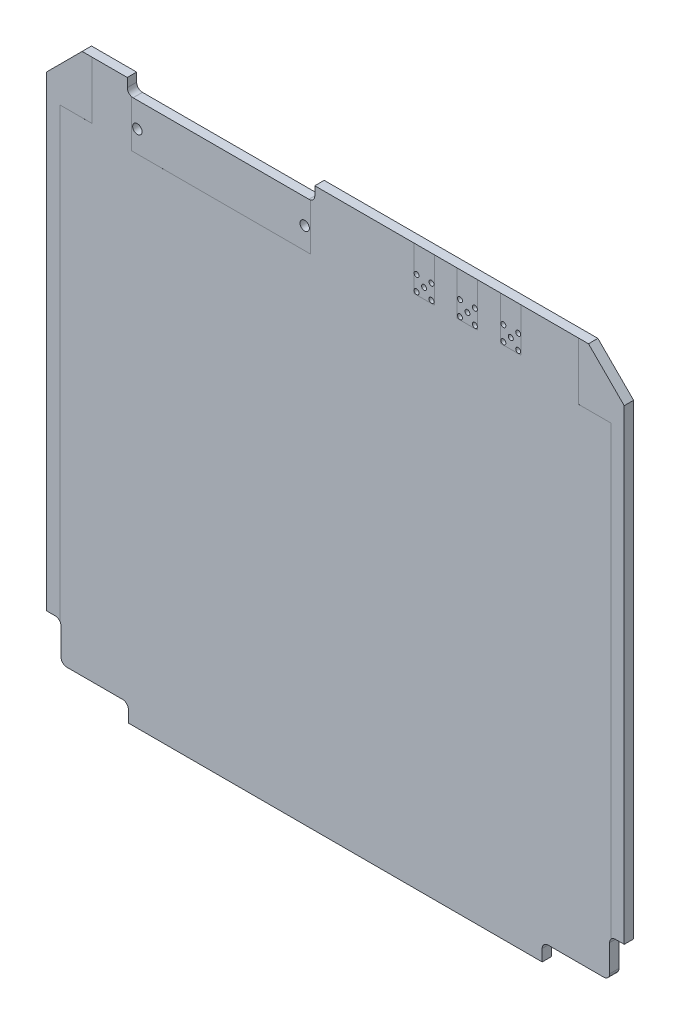
SolidWorks part; units mm, degrees
ref_plane "Front Plane" through (0, 0, 0) normal (0, 0, 1) x (1, 0, 0)
ref_plane "Top Plane" through (0, 0, 0) normal (0, 1, 0) x (1, 0, 0)
ref_plane "Right Plane" through (0, 0, 0) normal (1, 0, 0) x (0, 0, -1)
ref_plane "Plane4" through (0, 0, -0.0125) normal (0, 0, -1) x (-1, 0, 0)
sketch "Sketch1" plane through (0, 0, -0.0125) normal (0, 0, -1) x (-1, 0, 0)
  line L0 (35.3, -50) -> (35.3, -48)
  line L1 (36.3, -47) -> (45.8, -47)
  line L2 (46.8, -46) -> (46.8, -41.4)
  line L3 (47.8, -40.4) -> (49.3, -40.4)
  line L4 (49.3, -40.4) -> (49.3, 39.2)
  line L5 (49.3, 39.2) -> (43.2, 45.3)
  line L6 (43.2, 45.3) -> (35.5, 45.3)
  line L7 (35.5, 45.3) -> (35.5, 43.8)
  line L8 (34.5, 42.8) -> (4.5, 42.8)
  line L9 (3.5, 43.8) -> (3.5, 45.3)
  line L10 (3.5, 45.3) -> (-43.2, 45.3)
  line L11 (-43.2, 45.3) -> (-49.3, 39.2)
  line L12 (-49.3, 39.2) -> (-49.3, -40.4)
  line L13 (-49.3, -40.4) -> (-47.8, -40.4)
  line L14 (-46.8, -41.4) -> (-46.8, -46)
  line L15 (-45.8, -47) -> (-36.3, -47)
  line L16 (-35.3, -48) -> (-35.3, -50)
  line L17 (-35.3, -50) -> (35.3, -50)
  line L18 (0, -50) -> (0, 45.3) construction
  line L19 (19.5, 42.8) -> (19.5, 25.5258) construction
  line L20 (-13.87, 40.87) -> (-16.41, 38.33) construction
  line L21 (-21.27, 40.87) -> (-23.81, 38.33) construction
  line L22 (-28.67, 40.87) -> (-31.21, 38.33) construction
  arc A0 (35.3, -48) -> (36.3, -47) centre (36.3, -48) cw
  arc A1 (45.8, -47) -> (46.8, -46) centre (45.8, -46) ccw
  arc A2 (46.8, -41.4) -> (47.8, -40.4) centre (47.8, -41.4) cw
  arc A3 (35.5, 43.8) -> (34.5, 42.8) centre (34.5, 43.8) cw
  arc A4 (4.5, 42.8) -> (3.5, 43.8) centre (4.5, 43.8) cw
  arc A5 (-47.8, -40.4) -> (-46.8, -41.4) centre (-47.8, -41.4) cw
  arc A6 (-46.8, -46) -> (-45.8, -47) centre (-45.8, -46) ccw
  arc A7 (-36.3, -47) -> (-35.3, -48) centre (-36.3, -48) cw
  circle A8 centre (-21.27, 40.87) radius 0.425
  circle A9 centre (-23.81, 40.87) radius 0.425
  circle A10 centre (-22.54, 39.6) radius 0.425
  circle A11 centre (-13.87, 40.87) radius 0.425
  circle A12 centre (-23.81, 38.33) radius 0.425
  circle A13 centre (-16.41, 40.87) radius 0.425
  circle A14 centre (-15.14, 39.6) radius 0.425
  circle A15 centre (-21.27, 38.33) radius 0.425
  circle A16 centre (-28.67, 40.87) radius 0.425
  circle A17 centre (-31.21, 40.87) radius 0.425
  circle A18 centre (-16.41, 38.33) radius 0.425
  circle A19 centre (-29.94, 39.6) radius 0.425
  circle A20 centre (-31.21, 38.33) radius 0.425
  circle A21 centre (-28.67, 38.33) radius 0.425
  circle A22 centre (33.775, 38.54) radius 0.8
  circle A23 centre (5.225, 38.54) radius 0.8
  circle A24 centre (-13.87, 38.33) radius 0.425
  point P35 (-15.14, 39.6)
  dimension "D7" = 2.5
  dimension "D8" = 1.6
  dimension "D9" = 14.275
  dimension "D10" = 4.26
  dimension "D11" = 1
  dimension "D12" = 1
  dimension "D13" = 1
  dimension "D14" = 1
  dimension "D15" = 1
  dimension "D16" = 1
  dimension "D17" = 1
  dimension "D18" = 1
  dimension "D26" = 0.85
  dimension "D1" = 98.6
  dimension "D2" = 95.3
  dimension "D3" = 14
  dimension "D4" = 9.6
  dimension "D5" = 2.5
  dimension "D6" = 3
  dimension "D19" = 14
  dimension "D20" = 2.5
  dimension "D21" = 6.1
  dimension "D22" = 6.1
  dimension "D23" = 32
  dimension "D24" = 2.54
  dimension "D25" = 2.54
  dimension "D28" = 7.4
  dimension "D29" = 4.43
  dimension "D30" = 35.43
  dimension "D31" = 45
  dimension "D32" = 45
  dimension "D33" = 29.8
  dimension "D34" = 50
  dimension "D27" = 3
extrude "Boss-Extrude1" add sketch "Sketch1" against normal blind 1.6
sketch "thermalContacts_lower" plane through (0, 0, -0.0125) normal (0, 0, -1) x (-1, 0, 0)
  line L0 (-47, 35.5) -> (-47, -41.5) construction
  line L1 (-41.5, 35.5) -> (-41.5, 41.5) construction
  line L2 (-41.5, 35.5) -> (-47, 35.5) construction
  line L3 (-47, 35.5) -> (-47, -41.5)
  line L4 (-41.5, 35.5) -> (-41.5, 41.5)
  line L5 (-41.5, 35.5) -> (-47, 35.5)
  line L6 (47, 35.5) -> (47, -41.5) construction
  line L7 (41.5, 35.5) -> (47, 35.5) construction
  line L8 (41.5, 35.5) -> (41.5, 41.5) construction
  line L9 (47, 35.5) -> (47, -41.5)
  line L10 (41.5, 35.5) -> (47, 35.5)
  line L11 (41.5, 35.5) -> (41.5, 41.5)
  line L12 (41.5, 41.5) -> (41.5, 47) construction
  line L13 (41.5, 41.5) -> (49.5, 41.5) construction
  line L14 (41.5, 41.5) -> (41.5, 47)
  line L15 (41.5, 41.5) -> (49.5, 41.5) construction
  line L16 (-41.5, 41.5) -> (-41.5, 47) construction
  line L17 (-41.5, 41.5) -> (-49.5, 41.5) construction
  line L18 (-41.5, 41.5) -> (-41.5, 47)
  line L19 (-41.5, 41.5) -> (-49.5, 41.5) construction
  line L20 (47, -41.5) -> (59.8273, -41.5)
  line L21 (59.8273, -41.5) -> (59.8273, 47)
  line L22 (59.8273, 47) -> (41.5, 47)
  line L23 (-41.5, 47) -> (-56.1922, 47)
  line L24 (-56.1922, 47) -> (-56.1922, -41.5)
  line L25 (-56.1922, -41.5) -> (-47, -41.5)
sketch "thermalContacts_upper" plane through (0, 0, 1.5875) normal (0, 0, 1) x (1, 0, 0)
  line L3 (-47, 35.5) -> (-47, -41.5)
  line L4 (-41.5, 35.5) -> (-41.5, 41.5)
  line L5 (-41.5, 35.5) -> (-47, 35.5)
  line L9 (47, 35.5) -> (47, -41.5)
  line L10 (41.5, 35.5) -> (47, 35.5)
  line L11 (41.5, 35.5) -> (41.5, 41.5)
  line L14 (41.5, 41.5) -> (41.5, 47)
  line L15 (41.5, 41.5) -> (49.5, 41.5) construction
  line L18 (-41.5, 41.5) -> (-41.5, 47)
  line L19 (-41.5, 41.5) -> (-49.5, 41.5) construction
  line L20 (47, -41.5) -> (59.8273, -41.5)
  line L21 (59.8273, -41.5) -> (59.8273, 47)
  line L22 (59.8273, 47) -> (41.5, 47)
  line L23 (-41.5, 47) -> (-56.1922, 47)
  line L24 (-56.1922, 47) -> (-56.1922, -41.5)
  line L25 (-56.1922, -41.5) -> (-47, -41.5)
extrude "Cut-Extrude1" cut sketch "thermalContacts_lower" against normal blind 0.0001
extrude "Cut-Extrude2" cut sketch "thermalContacts_upper" against normal blind 0.0001
sketch "partFootprints" plane through (0, 0, 1.5875) normal (0, 0, 1) x (1, 0, 0)
  line L0 (-34.74, 34.84) -> (-34.74, 42.8292)
  line L1 (-4.26, 34.84) -> (-34.74, 34.84)
  line L2 (-41.5, 45.3) -> (-35.5, 45.3) construction
  line L3 (-36.1132, 45.3) -> (-39.5054, 45.3) construction
  line L4 (-4.26, 34.84) -> (-4.26, 42.8292)
  line L5 (-49.3, -40.4) -> (-49.3, 39.2) construction
  line L6 (13.39, 45.3) -> (13.39, 37.85)
  line L7 (13.39, 37.85) -> (16.89, 37.85)
  line L8 (16.89, 37.85) -> (16.89, 45.3)
  line L9 (16.89, 45.3) -> (13.39, 45.3)
  line L10 (20.79, 45.3) -> (20.79, 37.85)
  line L11 (20.79, 37.85) -> (24.29, 37.85)
  line L12 (24.29, 37.85) -> (24.29, 45.3)
  line L13 (24.29, 45.3) -> (20.79, 45.3)
  line L14 (28.19, 45.3) -> (28.19, 37.85)
  line L15 (28.19, 37.85) -> (31.69, 37.85)
  line L16 (31.69, 37.85) -> (31.69, 45.3)
  line L17 (31.69, 45.3) -> (28.19, 45.3)
  line L18 (49.3, -40.4) -> (49.3, 39.2) construction
  line L20 (-34.74, 42.8292) -> (-4.26, 42.8292)
  line L21 (-3.5, 45.3) -> (41.5, 45.3) construction
  arc A0 (-35.5, 43.8) -> (-34.5, 42.8) centre (-34.5, 43.8) ccw construction
  arc A1 (-4.5, 42.8) -> (-3.5, 43.8) centre (-4.5, 43.8) ccw construction
  dimension "D1" = 10.46
  dimension "D2" = 14.56
  dimension "D3" = 30.48
  dimension "D4" = 3.5
  dimension "D5" = 7.45
  dimension "D7" = 7.4
  dimension "D8" = 17.61
  dimension "D6" = 3
extrude "Cut-Extrude3" cut sketch "partFootprints" against normal blind 0.0001
